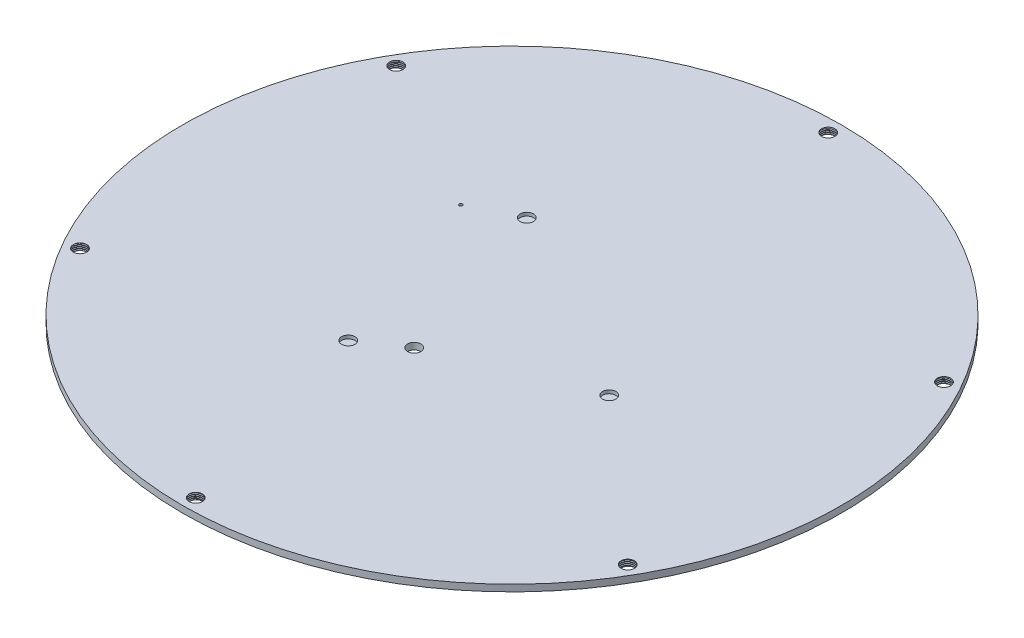
SolidWorks part; units mm, degrees
material "1060 Alloy"
ref_plane "Front Plane" through (0, 0, 0) normal (0, 0, 1) x (1, 0, 0)
ref_plane "Top Plane" through (0, 0, 0) normal (0, 1, 0) x (1, 0, 0)
ref_plane "Right Plane" through (0, 0, 0) normal (1, 0, 0) x (0, 0, -1)
sketch "Sketch1" plane through (0, 0, 0) normal (0, 1, 0) x (1, 0, 0)
  circle A0 centre (0, 0) radius 49.5
  circle A1 centre (0, 47.5) radius 1
  circle A2 centre (41.1362, 23.75) radius 1
  circle A3 centre (41.1362, -23.75) radius 1
  circle A4 centre (0, -47.5) radius 1
  circle A5 centre (-41.1362, -23.75) radius 1
  circle A6 centre (-41.1362, 23.75) radius 1
  point P17 (0, 0)
  dimension "D1" = 99
  dimension "D2" = 2
  dimension "D3" = 47.5
  dimension "D4" = 6
extrude "Boss-Extrude1" add sketch "Sketch1" along normal blind 1
thread "Thread1" pitch 0.25 method cut profile "Thread Profile1" start angle 0, offset 0, length 10, pitch 0.25, diameter 2
ref_plane "Plane1" through (-42.1362, 1, 23.75) normal (0, 0, 1) x (-1, 0, 0)
sketch "Thread Profile1" plane through (-42.1362, 1, 23.75) normal (0, 0, 1) x (-1, 0, 0)
  line L0 (0, 0) -> (0, 0.25) construction
  line L1 (0, 0) -> (0.1353, 0.0781)
  line L2 (0.1353, 0.0781) -> (0.1353, 0.1094)
  line L3 (0.1353, 0.1094) -> (0, 0.1875)
  line L4 (0.1353, 0.0937) -> (0, 0.0937) construction
  line L11 (0, 0) -> (0, 0.1875)
  point P2 (0, 0)
  dimension "Pitch" = 0.25
  dimension "Profile_Angle" = 60
  dimension "Profile_Land" = 0.0312
  dimension "Profile_Height" = 0.1353
pattern_circular "CirPattern1" count 6 over 360 about axis through (0, 0, 0) along (0, 1, 0) of "Thread1"
sketch "Sketch2" plane through (0, 1, 0) normal (0, 1, 0) x (1, 0, 0)
  line L0 (12.1829, 21.1013) -> (0, 0) construction
  line L1 (0, 0) -> (-13.509, -23.3983) construction
  line L2 (0, 0) -> (-7.5117, -28.0339) construction
  line L3 (0, 0) -> (0, -23.2906) construction
  line L4 (0, -23.2906) -> (0, 0) construction
  line L5 (0, 0) -> (-12.9568, 7.4806) construction
  circle A1 centre (-3.1058, -11.5911) radius 1
  circle A2 centre (-18.1865, 10.5) radius 0.25
  dimension "D1" = 0.5
  dimension "D3" = 2
  dimension "D2" = 21
  dimension "D4" = 12
  dimension "D5" = 15
  dimension "D6" = 30
  dimension "D7" = 90
  dimension "D8" = 0
extrude "Cut-Extrude1" cut sketch "Sketch2" against normal through all both and the other way through all
sketch "Sketch3" plane through (0, 1, 0) normal (0, 1, 0) x (1, 0, 0)
  line L0 (17.7265, -3.1257) -> (0, 0) construction
  line L1 (0, 0) -> (-11.5702, 13.7888) construction
  line L2 (-11.5702, 13.7888) -> (0, 0) construction
  line L3 (0, 0) -> (-9, -15.5885) construction
  line L4 (-9, -15.5885) -> (0, 0) construction
  line L5 (0, 0) -> (41.1362, -23.75) construction
  circle A0 centre (0, 0) radius 18
  circle A1 centre (-9, -15.5885) radius 1
  circle A2 centre (17.7265, -3.1257) radius 1
  circle A3 centre (-11.5702, 13.7888) radius 1
  dimension "D1" = 36
  dimension "D2" = 2
  dimension "D3" = 2
  dimension "D4" = 2
  dimension "D5" = 90
  dimension "D6" = 110
  dimension "D7" = 140
extrude "Cut-Extrude2" cut sketch "Sketch3" against normal blind 0.5 contours A0 A2 | A0 A2 | A0 A1 | A0 A1 | A0 A3 | A0 A3 region at (-11.2942, 1, -13.4599) region at (-11.8397, 1, -14.1101) region at (18.1395, 1, 3.1985) region at (17.3037, 1, 3.0511) region at (-8.7853, 1, 15.2166) region at (-9.2097, 1, 15.9516)
